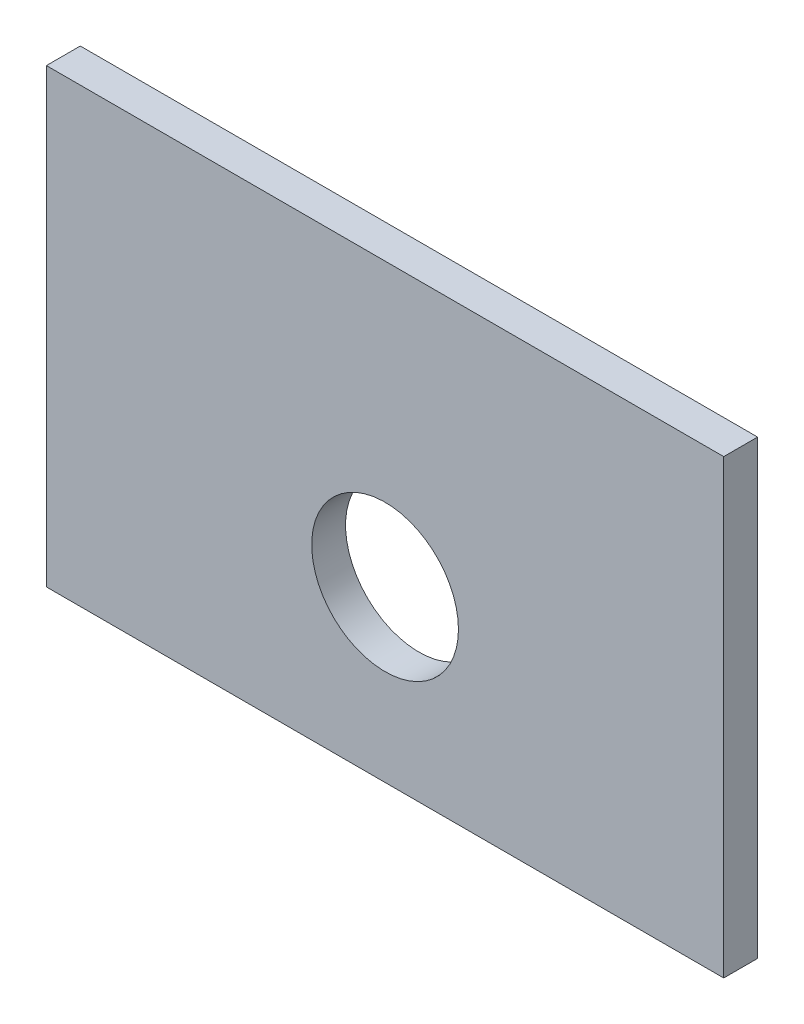
SolidWorks part; units mm, degrees
ref_plane "Front Plane" through (0, 0, 0) normal (0, 0, 1) x (1, 0, 0)
ref_plane "Top Plane" through (0, 0, 0) normal (0, 1, 0) x (1, 0, 0)
ref_plane "Right Plane" through (0, 0, 0) normal (1, 0, 0) x (0, 0, -1)
sketch "Sketch1" plane through (0, 0, 0) normal (0, 0, 1) x (1, 0, 0)
  line L1 (0, 0) -> (30, 0)
  line L2 (0, 0) -> (0, 20)
  line L3 (0, 20) -> (30, 20)
  line L4 (30, 0) -> (30, 20)
  circle A0 centre (15, 7.5) radius 3.25
  point P7 (15, 0)
  dimension "D1" = 6.5
  dimension "D2" = 7.5
  dimension "D3" = 30
  dimension "D4" = 20
base flange "Base-Flange1" sketch "Sketch1" thickness 1.5 reverse thickness direction no parameters "D1"=2
sketch "Bend-Lines1" [suppressed] plane through (0, 0, 0) normal (0, 1, 0) x (1, 0, 0)
sketch "Bounding-Box1" [suppressed] plane through (0, 0, 0) normal (0, 1, 0) x (1, 0, 0)
sheet metal parameters "Sheet-Metal1" thickness 1.5 parameters "D1"=2
flat pattern "Flat-Pattern1" [suppressed]
sketch "Bend-Lines2" plane through (0, 0, 0) normal (0, 1, 0) x (1, 0, 0)
sketch3d "Bounding-Box2" [suppressed]
  line L0 (0, 0, 0) -> (-30, 0, 0) construction
  line L1 (0, 20, 0) -> (-30, 20, 0) construction
  line L2 (0, 0, 0) -> (0, 20, 0) construction
  line L3 (-30, 0, 0) -> (-30, 20, 0) construction
